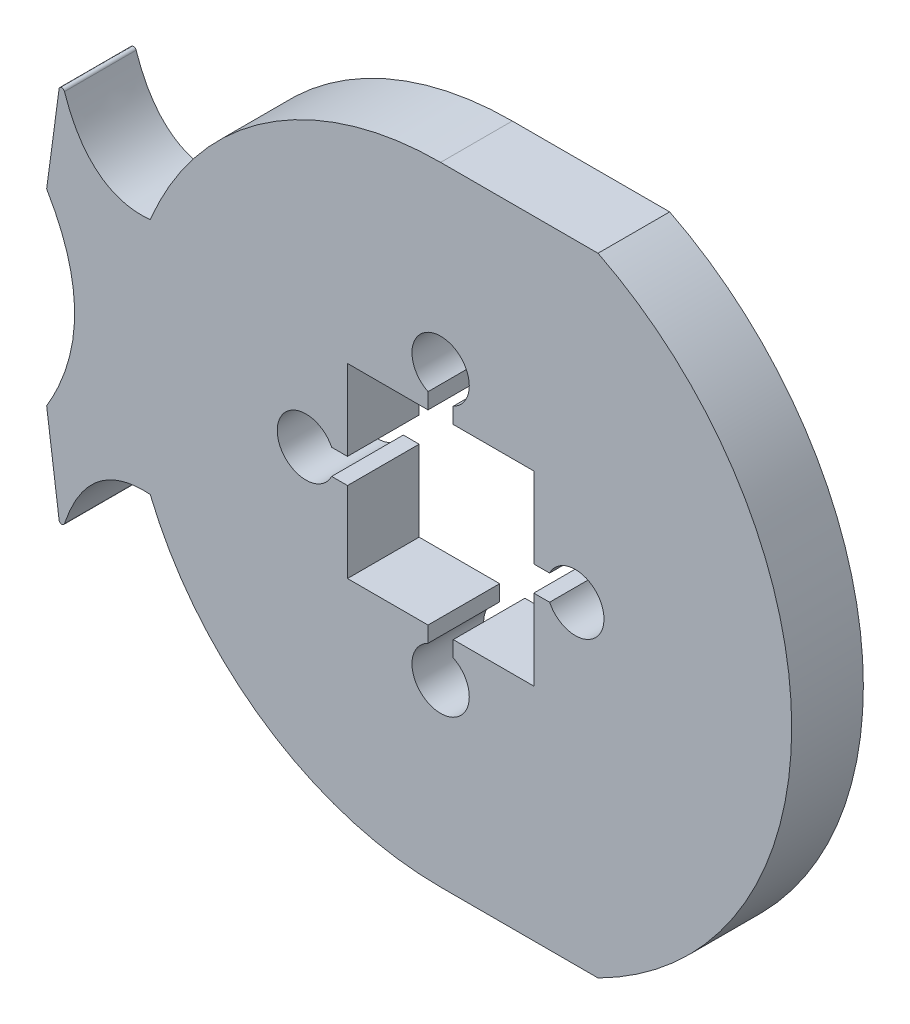
SolidWorks part; units mm, degrees
material "AISI 1020"
ref_plane "Front Plane" through (0, 0, 0) normal (0, 0, 1) x (1, 0, 0)
ref_plane "Top Plane" through (0, 0, 0) normal (0, 1, 0) x (1, 0, 0)
ref_plane "Right Plane" through (0, 0, 0) normal (1, 0, 0) x (0, 0, -1)
other "Center of Mass"
sketch "Sketch1" plane through (0, 0, 0) normal (0, 0, 1) x (1, 0, 0)
  line L0 (-11.938, 0) -> (0, 0) construction
  line L1 (-8.255, 8.255) -> (8.255, 8.255)
  line L2 (-8.255, 8.255) -> (-8.255, -8.255)
  line L3 (-8.255, -8.255) -> (8.255, -8.255)
  line L4 (8.255, 8.255) -> (8.255, -8.255)
  line L5 (0, 0) -> (0, 11.938) construction
  line L6 (11.938, 0) -> (0, 0) construction
  line L7 (0, 0) -> (0, -11.938) construction
  line L9 (-9.6571, 1.1176) -> (9.6571, 1.1176)
  line L10 (-9.6571, 1.1176) -> (-9.6571, -1.1176)
  line L11 (-9.6571, -1.1176) -> (9.6571, -1.1176)
  line L12 (9.6571, 1.1176) -> (9.6571, -1.1176)
  line L13 (-1.1176, 9.6571) -> (1.1176, 9.6571)
  line L14 (-1.1176, 9.6571) -> (-1.1176, -9.6571)
  line L15 (-1.1176, -9.6571) -> (1.1176, -9.6571)
  line L16 (1.1176, 9.6571) -> (1.1176, -9.6571)
  line L17 (0, 27.813) -> (13.9492, 27.813)
  line L18 (0, -27.813) -> (13.9492, -27.813)
  line L19 (-33.8048, 16.6086) -> (-34.9172, 8.3198)
  line L20 (-34.9172, -8.3198) -> (-33.8048, -16.6086)
  circle A1 centre (0, 11.938) radius 2.54
  circle A2 centre (0, -11.938) radius 2.54
  circle A3 centre (11.938, 0) radius 2.54
  circle A4 centre (-11.938, 0) radius 2.54
  arc A36 (8.7964, -10.0222) -> (10.0222, -8.7964) centre (0, 0) ccw
  arc A37 (-25.7359, -10.5464) -> (0, -27.813) centre (0, 0) ccw
  arc A39 (-33.3353, 16.5776) -> (-33.8048, 16.6086) centre (-33.5763, 16.4976) ccw
  arc A40 (-33.3353, -16.5776) -> (-33.8048, -16.6086) centre (-33.5763, -16.4976) cw
  arc A41 (13.9492, -27.813) -> (13.9492, 27.813) centre (0, 0) ccw
  arc A42 (0, 27.813) -> (-25.7359, 10.5464) centre (0, 0) ccw
  spline S0 degree 3 poles (-33.3353, 16.5776) (-31.8977, 12.2441) (-29.218, 10.1877) (-25.7359, 10.5464) knots 0.081541 0.081541 0.081541 0.081541 1 1 1 1
  spline S1 degree 3 poles (-33.3353, -16.5776) (-31.8977, -12.2441) (-29.2304, -10.2896) (-25.7359, -10.5464) knots 0.081541 0.081541 0.081541 0.081541 1 1 1 1
  spline S2 degree 2 poles (-34.9172, 8.3198) (-29.9564, 0) (-34.9172, -8.3198) knots 0 0 0 1 1 1
  point P7 (8.255, 0)
  point P8 (0, 8.255)
  point P54 (0, 0)
  point P70 (0, 0)
  point P77 (0, 0)
  dimension "D4" = 5.08
  dimension "D10" = 55.626
  dimension "D12" = 0.254
  dimension "D14" = 62.23
  dimension "D1" = 16.51
  dimension "D3" = 11.938
  dimension "D5" = 2.2352
extrude "Boss-Extrude1" add sketch "Sketch1" along normal blind 6.35 contours A4 L9 L2 L1 L14 A1 L16 L4 A3 L11 L3 A2 region at (6.9746, 26.9496, 0)
